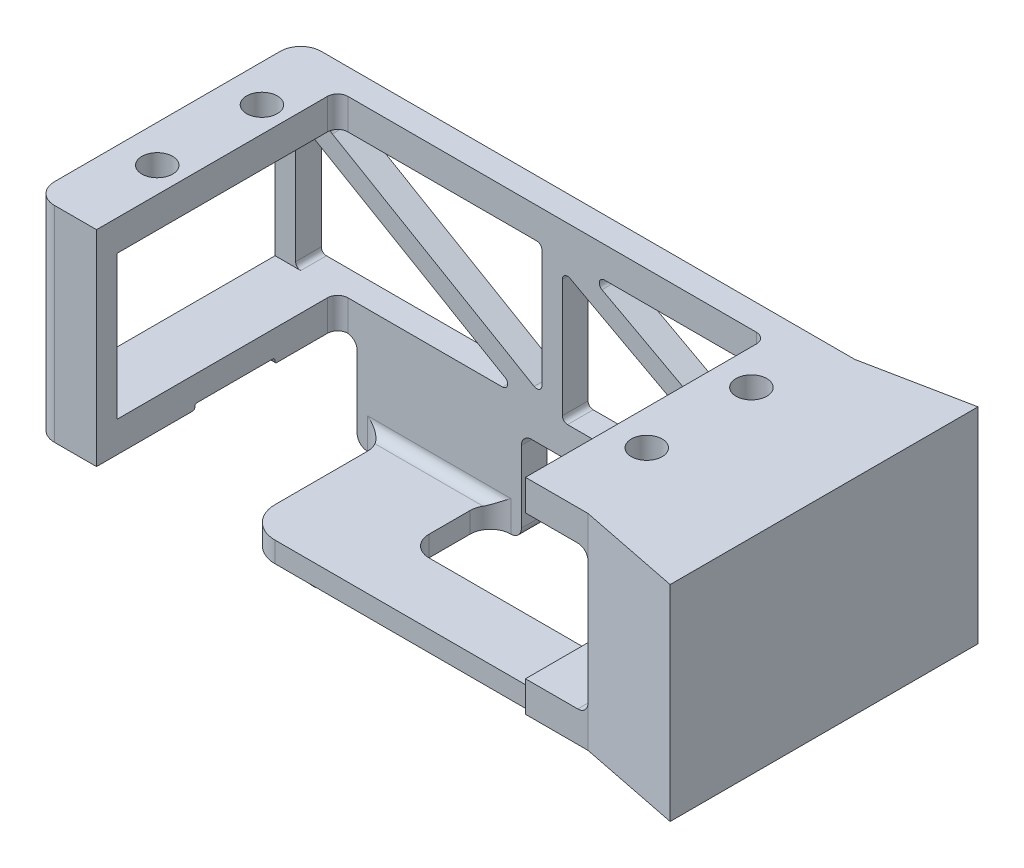
SolidWorks part; units mm, degrees
ref_plane "Plano frontal" through (0, 0, 0) normal (0, 0, 1) x (1, 0, 0)
ref_plane "Plano superior" through (0, 0, 0) normal (0, 1, 0) x (1, 0, 0)
ref_plane "Plano direito" through (0, 0, 0) normal (1, 0, 0) x (0, 0, -1)
sketch "Esboço1" plane through (0, 0, 0) normal (0, 1, 0) x (1, 0, 0)
  line L1 (-4.6429, -13) -> (5.3571, -15)
  line L2 (-4.6429, -13) -> (-4.6429, 13)
  line L3 (-4.6429, 13) -> (5.3571, 15)
  line L4 (5.3571, -15) -> (5.3571, 15)
  line L5 (-4.6429, -13) -> (5.3571, 15) construction
  line L6 (-4.6429, 13) -> (5.3571, -15) construction
  point P0 (0, 0)
  point P6 (-4.6429, 0)
  dimension "D1" = 30
  dimension "D2" = 10
  dimension "D3" = 26
extrude "Ressalto-extrusão1" add sketch "Esboço1" along normal mid plane 20
sketch "Esboço2" plane through (0, 10, 0) normal (0, 1, 0) x (1, 0, 0)
  line L1 (-4.6429, 13) -> (-58.6429, 13)
  line L2 (-4.6429, 13) -> (-4.6429, -13)
  line L3 (-4.6429, -13) -> (-58.6429, -13)
  line L4 (-58.6429, 13) -> (-58.6429, -13)
  dimension "D1" = 54
extrude "Ressalto-extrusão2" add sketch "Esboço2" against normal blind 3
sketch "Esboço4" plane through (0, -10, 0) normal (0, -1, 0) x (1, 0, 0)
  line L0 (-4.6429, -13) -> (-4.6429, 13) construction
  line L1 (-4.6429, 13) -> (-58.6429, 13)
  line L2 (-4.6429, 13) -> (-4.6429, -13)
  line L3 (-4.6429, -13) -> (-58.6429, -13)
  line L4 (-58.6429, 13) -> (-58.6429, -13)
  line L5 (-58.6429, -13) -> (-58.6429, 13) construction
extrude "Ressalto-extrusão3" add sketch "Esboço4" against normal blind 3
sketch "Esboço3" plane through (0, 7, 0) normal (0, -1, 0) x (1, 0, 0)
  line L0 (-58.6429, 13) -> (-4.6429, 13) construction
  line L1 (-52.5429, -10.5) -> (-10.7429, -10.5)
  line L2 (-52.5429, -10.5) -> (-52.5429, 10.5)
  line L3 (-52.5429, 10.5) -> (-10.7429, 10.5)
  line L4 (-10.7429, -10.5) -> (-10.7429, 10.5)
  line L5 (-52.5429, -10.5) -> (-10.7429, 10.5) construction
  line L6 (-52.5429, 10.5) -> (-10.7429, -10.5) construction
  line L8 (-52.5429, 10.5) -> (-10.7429, 10.5)
  line L9 (-52.5429, 10.5) -> (-52.5429, 13)
  line L10 (-52.5429, 13) -> (-10.7429, 13)
  line L11 (-10.7429, 10.5) -> (-10.7429, 13)
  point P0 (-31.6429, 0)
  point P7 (-31.6429, 13)
  line M7 (-4.6429, 13) -> (-58.6429, 13)
  dimension "D1" = 41.8
  dimension "D2" = 21
extrude "Corte-extrusão1" cut sketch "Esboço3" against normal up to next and the other way up to next contours L1 L4 L3 L2 | L3 L11 L9 M7 region at (-31.6429, 7, 0) region at (-31.6429, 7, 11.75)
sketch "Esboço5" plane through (0, 0, -13) normal (0, 0, -1) x (-1, 0, 0)
  line L0 (4.6429, 7) -> (58.6429, 7) construction
  line L1 (58.6429, -7) -> (56.6429, -7)
  line L2 (58.6429, -7) -> (58.6429, 7)
  line L3 (58.6429, 7) -> (56.6429, 7)
  line L4 (56.6429, -7) -> (56.6429, 7)
  line L5 (58.6429, -7) -> (4.6429, -7) construction
  line L6 (30.6429, -7) -> (32.6429, -7)
  line L7 (30.6429, -7) -> (30.6429, 7)
  line L8 (30.6429, 7) -> (32.6429, 7)
  line L9 (32.6429, -7) -> (32.6429, 7)
  line L10 (32.6429, -7) -> (56.6429, 7)
  line L12 (32.6429, -5.8423) -> (54.6582, 7)
  line L13 (34.6275, -7) -> (56.6429, 5.8423)
  line L15 (4.6429, -7) -> (30.6429, 7)
  line L19 (4.6429, -5.8642) -> (28.5336, 7)
  line L20 (4.6429, 7) -> (4.6429, -7) construction
  line L21 (30.6429, 5.8642) -> (6.7521, -7)
  line L22 (4.6429, -5.8642) -> (4.6429, -7)
  line L23 (6.7521, -7) -> (4.6429, -7)
  line L24 (28.5336, 7) -> (30.6429, 7)
  line L25 (30.6429, 5.8642) -> (30.6429, 7)
  line L26 (28.5336, 7) -> (30.6429, 7)
  line L27 (56.6429, 7) -> (54.6582, 7)
  line L28 (34.6275, -7) -> (32.6429, -7)
  point P14 (31.6429, -7)
  point P15 (31.6429, -7)
  line M23 (4.6429, 7) -> (58.6429, 7)
  dimension "D1" = 2
  dimension "D2" = 2
  dimension "D3" = 1
  dimension "D4" = 1
  dimension "D5" = 1
  dimension "D6" = 1
extrude "Ressalto-extrusão4" add sketch "Esboço5" against normal up to surface (2.5 mm away) contours L6 L9 L7 M23 | L12 L9 L10 M23 | L28 L13 L4 L10 | L4 L1 L2 M23 | L23 L21 L7 L15 | L19 L22 L15 M23 region at (-57.6429, 0, -13) region at (-45.1319, -0.2853, -13) region at (-44.1538, 0.2853, -13) region at (-31.6429, 0, -13) region at (-18.1627, -0.2799, -13) region at (-17.123, 0.2799, -13) up to face at (-31.6429, 8.5, -10.5)
sketch "Esboço6" plane through (0, 0, -13) normal (0, 0, -1) x (-1, 0, 0)
  line L0 (58.6429, -10) -> (4.6429, -10) construction
  line L1 (34.6429, -10) -> (50.6429, -10)
  line L2 (34.6429, -10) -> (34.6429, -19)
  line L3 (34.6429, -19) -> (50.6429, -19)
  line L4 (50.6429, -10) -> (50.6429, -19)
  line L5 (4.6429, 10) -> (58.6429, 10) construction
  line L6 (58.6429, -10) -> (58.6429, 10) construction
  point P8 (42.6429, -10)
  dimension "D1" = 29
  dimension "D2" = 16
  dimension "D3" = 16
extrude "Ressalto-extrusão5" add sketch "Esboço6" against normal up to surface (2.5 mm away) up to face at (-33.8247, -0.6364, -10.5)
sketch "Esboço7" plane through (0, 0, -10.5) normal (0, 0, 1) x (1, 0, 0)
  line L0 (-34.6429, -10) -> (-34.6429, -19) construction
  line L1 (-50.6429, -19) -> (-34.6429, -19)
  line L2 (-50.6429, -19) -> (-50.6429, -17)
  line L3 (-50.6429, -17) -> (-34.6429, -17)
  line L4 (-34.6429, -19) -> (-34.6429, -17)
  line L5 (-10.7429, 10) -> (-52.5429, 10) construction
  dimension "D1" = 27
extrude "Ressalto-extrusão6" add sketch "Esboço7" along normal blind 14
sketch "Esboço9" plane through (0, -19, 0) normal (0, -1, 0) x (1, 0, 0)
  line L0 (-42.6429, 0) -> (0, 0) construction
sketch "Esboço8" plane through (0, -19, 0) normal (0, -1, 0) x (1, 0, 0)
  line L0 (-50.6429, 3.5) -> (-34.6429, 3.5) construction
  line L1 (-45.1429, 0) -> (-40.1429, 0)
  circle A0 centre (-42.6429, 0) radius 2.5
  point P6 (-42.6429, 3.5)
  dimension "D1" = 5
revolve "Revolução1" add sketch "Esboço8" angle 180 about L0 region at (-42.6429, -19, -1.061) reverse direction yes
sketch "Esboço10" plane through (0, -17, 0) normal (0, 1, 0) x (1, 0, 0)
  line L1 (-50.6429, -3.5) -> (-47.6429, -3.5)
  line L2 (-50.6429, -3.5) -> (-50.6429, 10.5)
  line L3 (-50.6429, 10.5) -> (-47.6429, 10.5)
  line L4 (-47.6429, -3.5) -> (-47.6429, 10.5)
  line L5 (-34.6429, 10.5) -> (-50.6429, 10.5) construction
  line L6 (-34.6429, -3.5) -> (-37.6429, -3.5)
  line L7 (-34.6429, -3.5) -> (-34.6429, 10.5)
  line L8 (-34.6429, 10.5) -> (-37.6429, 10.5)
  line L9 (-37.6429, -3.5) -> (-37.6429, 10.5)
  line L10 (-34.6429, 10.5) -> (-50.6429, 10.5) construction
  dimension "D1" = 3
  dimension "D2" = 3
extrude "Corte-extrusão2" cut sketch "Esboço10" against normal up to next
sketch "Sketch1" plane through (-37.6429, 0, 0) normal (1, 0, 0) x (0, 0, -1)
  line L0 (-2.5, -19) -> (2.5, -19) construction
  line L1 (-3.5, -17) -> (2.5, -17)
  line L2 (-3.5, -17) -> (-3.5, -19)
  line L3 (-3.5, -19) -> (2.5, -19)
  line L4 (2.5, -17) -> (2.5, -19)
  dimension "D1" = 6
extrude "Boss-Extrude1" add sketch "Sketch1" along normal up to surface (26.9 mm away) up to face at (-10.7429, -8.5, 1.25)
sketch "Sketch2" plane through (-10.7429, 0, 0) normal (1, 0, 0) x (0, 0, -1)
  line L1 (-3.5, -17) -> (2.5, -17)
  line L2 (-3.5, -17) -> (-3.5, -19)
  line L3 (-3.5, -19) -> (2.5, -19)
  line L4 (2.5, -17) -> (2.5, -19)
extrude "Boss-Extrude2" add sketch "Sketch2" along normal blind 2
sketch "Sketch3" plane through (0, -17, 0) normal (0, 1, 0) x (1, 0, 0)
  line L0 (-8.7429, 2.5) -> (-37.6429, 2.5) construction
  line L1 (-8.7429, -3.5) -> (-10.7429, -3.5)
  line L2 (-8.7429, -3.5) -> (-8.7429, 2.5)
  line L3 (-8.7429, 2.5) -> (-10.7429, 2.5)
  line L4 (-10.7429, -3.5) -> (-10.7429, 2.5)
  line L5 (-10.7429, 10.5) -> (-10.7429, -13) construction
extrude "Boss-Extrude3" add sketch "Sketch3" along normal up to surface (7 mm away) up to face at (-53.9429, -10, -3.5)
fillet "Fillet1" radius 2 3 edges at (-9.7429, -10, -2.5) (-9.7429, -10, 3.5) (-8.7429, -10, 0.5)
fillet "Fillet4" radius 2 5 edges at (-37.6429, -18, -2.5) (-47.6429, -18, -10.5) (-37.6429, -18, -10.5) (-8.7429, -19, 0.5) (-10.7429, -17, 0.5)
fillet "Fillet6" radius 3 1 edges at (-47.6429, -18, 3.5)
fillet "Fillet7" radius 1 4 edges at (-50.6429, -10, -11.75) (-34.6429, -19, -11.75) (-34.6429, -10, -11.75) (-50.6429, -19, -11.75)
sketch "Sketch5" plane through (0, 7, 0) normal (0, -1, 0) x (1, 0, 0)
  line L0 (-52.5429, -10.5) -> (-52.5429, 13) construction
  line L1 (-58.6429, 13) -> (-52.5429, 13)
  line L2 (-58.6429, 13) -> (-58.6429, 11)
  line L3 (-58.6429, 11) -> (-52.5429, 11)
  line L4 (-52.5429, 13) -> (-52.5429, 11)
  dimension "D1" = 2
extrude "Boss-Extrude4" add sketch "Sketch5" along normal up to surface (14 mm away) up to face at (-50.614, -7, -5.25)
sketch "Sketch6" plane through (0, 10, 0) normal (0, 1, 0) x (1, 0, 0)
  line L0 (-52.5429, -13) -> (-52.5429, 10.5) construction
  line L1 (-4.6429, 13) -> (-58.6429, 13) construction
  circle A0 centre (-55.0229, 5.6) radius 1.5
  circle A1 centre (-7.3229, 5.6) radius 1.5
  point P8 (0, 0)
  dimension "D1" = 3
  dimension "D4" = 3
  dimension "D2" = 2.48
  dimension "D3" = 7.4
  dimension "D5" = 47.7
extrude "Cut-Extrude1" cut sketch "Sketch6" against normal up to next
pattern_linear "LPattern1" count 2 spacing 10.2 along (0, 0, 1) of "Cut-Extrude1"
sketch "Sketch7" plane through (0, -10, 0) normal (0, -1, 0) x (1, 0, 0)
  line L0 (-52.5429, 13) -> (-58.6429, 13) construction
  line L1 (-58.6429, 3.4247) -> (-52.5429, 3.4247)
  line L2 (-58.6429, 3.4247) -> (-58.6429, -4.3753)
  line L3 (-58.6429, -4.3753) -> (-52.5429, -4.3753)
  line L4 (-52.5429, 3.4247) -> (-52.5429, -4.3753)
  line L5 (-58.6429, 3.4247) -> (-52.5429, -4.3753) construction
  line L6 (-58.6429, -4.3753) -> (-52.5429, 3.4247) construction
  line L7 (-52.5429, -10.5) -> (-52.5429, 13) construction
  line L8 (-58.6429, 13) -> (-58.6429, -13) construction
  point P0 (-55.5929, -0.4753)
  dimension "D1" = 13.4753
  dimension "D2" = 7.8
extrude "Cut-Extrude2" cut sketch "Sketch7" against normal blind 0.5
fillet "Fillet8" radius 0.2 4 edges at (-55.5929, -10, -4.3753) (-55.5929, -10, 3.4247) (-55.5929, -9.5, -4.3753) (-55.5929, -9.5, 3.4247)
fillet "Fillet11" radius 1 6 edges at (-52.5429, -8.5, -10.5) (-10.7429, -8.5, -10.5) (-52.5429, 8.5, -10.5) (-10.7429, 8.5, -10.5) (-4.6429, 7, 0) (-4.6429, -7, 1.25)
fillet "Fillet13" radius 2 2 edges at (-58.6429, 0, 13) (-58.6429, 0, -13)
fillet "Fillet14" radius 0.5 11 edges at (-4.6429, -5.8642, -11.75) (-28.5336, 7, -11.75) (-6.7521, -7, -11.75) (-30.6429, -7, -11.75) (-30.6429, 5.8642, -11.75) (-32.6429, -5.8423, -11.75) (-32.6429, 7, -11.75) (-54.6582, 7, -11.75) (-34.6275, -7, -11.75) (-56.6429, -7, -11.75) (-56.6429, 5.8423, -11.75)
fillet "Fillet15" radius 1 1 edges at (-42.6429, -17, -10.5)
equation "\"Folga_total\"= 1mm'Folga devido ao encaixe"
equation "\"D1@Esboço3\"=\"Folga_total\"+40.8"
equation "\"D2@Esboço3\"=\"Folga_total\"+20"
equation "\"D1@Esboço7\"=\"Folga_total\"+26"
equation "\"D1@Esboço10\"=\"D2@Esboço10\""
equation "\"D4@Sketch6\"=\"D1@Sketch6\""
